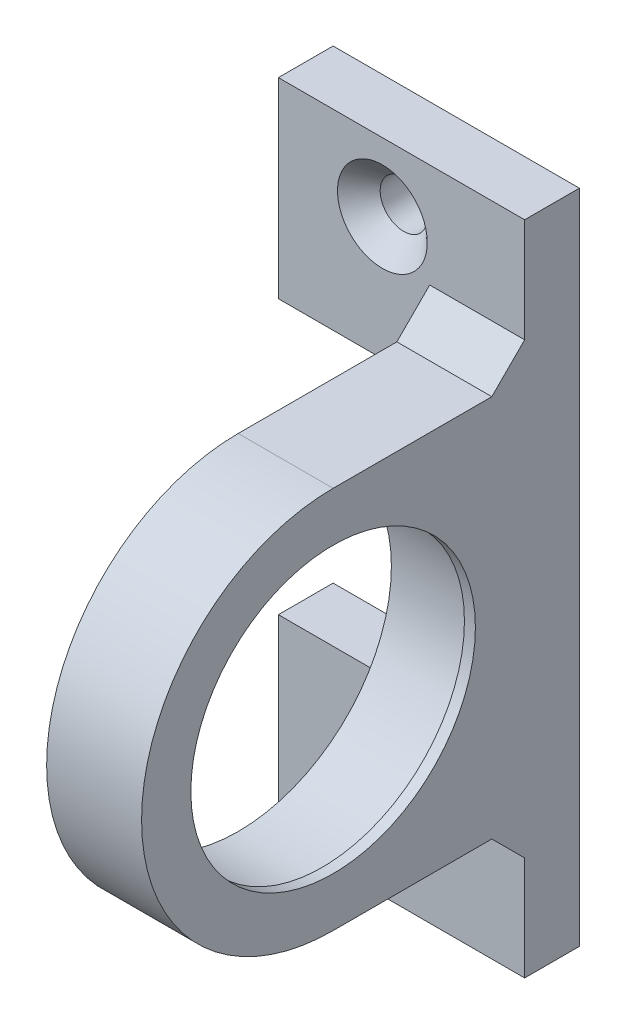
SolidWorks part; units mm, degrees
ref_plane "前视基准面" through (0, 0, 0) normal (0, 0, 1) x (1, 0, 0)
ref_plane "上视基准面" through (0, 0, 0) normal (0, 1, 0) x (1, 0, 0)
ref_plane "右视基准面" through (0, 0, 0) normal (1, 0, 0) x (0, 0, -1)
sketch "草图2" plane through (0, 0, 0) normal (0, 0, 1) x (1, 0, 0)
  line L0 (-14.7736, 24.3382) -> (-14.7736, -35.6618)
  line L1 (-14.7736, -35.6618) -> (30.2264, -35.6618)
  line L2 (7.7264, -35.6618) -> (7.7264, -18.1618)
  line L3 (21.55, -18.1618) -> (-6.0971, -18.1618)
  line L4 (-6.0971, -18.1618) -> (-6.0971, 6.8382)
  line L5 (-6.0971, 6.8382) -> (21.55, 6.8382)
  line L6 (7.7264, 6.8382) -> (7.7264, 24.3382)
  line L7 (30.2264, 24.3382) -> (-14.7736, 24.3382)
  line L8 (7.7264, 28.8603) -> (7.7264, -39.8897) construction
  line L9 (21.55, -18.1618) -> (21.55, 6.8382)
  line L10 (30.2264, 24.3382) -> (30.2264, -35.6618)
  line L11 (-18.1559, -5.6618) -> (33.2411, -5.6618) construction
  line L12 (44.0218, -5.6618) -> (44.0218, 26.2521) construction
  point P16 (-6.0971, -5.6618)
  point P17 (-14.7736, -5.6618)
  dimension "D1" = 45
  dimension "D2" = 25
  dimension "D3" = 60
extrude "凸台-拉伸2" add sketch "草图2" along normal blind 5 contours L6 L7 L0 L1 L2 L3 L4 L5 | L10 L7 L6 L5 L9 L3 L2 L1 region at (-3.5236, 23.6974, 0) region at (18.9764, 23.6974, 0)
sketch "草图4" plane through (0, 0, 5) normal (0, 0, 1) x (1, 0, 0)
  line L0 (-18.165, -5.6618) -> (33.9165, -5.6618) construction
  line L1 (-14.7736, 24.3382) -> (-14.7736, -35.6618) construction
  line L2 (-14.7736, -23.1618) -> (-6.0971, -23.1618)
  line L3 (-14.7736, -23.1618) -> (-14.7736, 11.8382)
  line L4 (-14.7736, 11.8382) -> (-6.0971, 11.8382)
  line L5 (-6.0971, -23.1618) -> (-6.0971, 11.8382)
  line L6 (-6.0971, -18.1618) -> (-6.0971, 6.8382) construction
  line L7 (7.7264, -39.813) -> (7.7264, 28.1228) construction
  line L8 (30.2264, 11.8382) -> (21.55, 11.8382)
  line L9 (21.55, -23.1618) -> (21.55, 11.8382)
  line L10 (30.2264, -23.1618) -> (21.55, -23.1618)
  line L11 (30.2264, -23.1618) -> (30.2264, 11.8382)
  point P17 (-14.7736, -5.6618)
  dimension "D1" = 35
extrude "凸台-拉伸15" add sketch "草图4" along normal blind 35
sketch "草图5" plane through (-14.7736, 0, 0) normal (-1, 0, 0) x (0, 0, 1)
  line L0 (0, -5.6618) -> (40, -5.6618)
  line L1 (0, 24.3382) -> (0, -35.6618) construction
  line L2 (40, 11.8382) -> (40, -23.1618) construction
  line L3 (22.5, 11.8382) -> (40, 11.8382)
  line L4 (40, 11.8382) -> (40, -23.1618)
  line L5 (40, -23.1618) -> (22.5, -23.1618)
  circle A0 centre (22.5, -5.6618) radius 17.5
  line M5 (5, -23.1618) -> (40, -23.1618)
  line M6 (40, -23.1618) -> (40, 11.8382)
  line M7 (40, 11.8382) -> (5, 11.8382)
  dimension "D1" = 35
extrude "切除-拉伸1" cut sketch "草图5" against normal blind 45 contours A0 M5 M6 | A0 M6 M7 region at (-14.7736, 7.9293, 36.0911) region at (-14.7736, -19.2528, 36.0911)
sketch "草图6" plane through (-14.7736, 0, 0) normal (-1, 0, 0) x (0, 0, 1)
  circle A0 centre (22.5, -5.6618) radius 14
  dimension "D1" = 28
extrude "切除-拉伸2" cut sketch "草图6" against normal blind 45
fillet "圆角1" radius 5 4 edges at (-6.0971, 6.8382, 2.5) (21.55, 6.8382, 2.5) (-6.0971, -18.1618, 2.5) (21.55, -18.1618, 2.5)
sketch "草图7" plane through (-6.0971, 0, 0) normal (1, 0, 0) x (0, 0, -1)
  circle A0 centre (-22.5, -5.6618) radius 15
  circle A1 centre (-22.5, -5.6618) radius 13
extrude "凸台-拉伸16" add sketch "草图7" against normal blind 1
sketch "草图8" plane through (21.55, 0, 0) normal (-1, 0, 0) x (0, 0, 1)
  circle A0 centre (22.5, -5.6618) radius 15
  circle A1 centre (22.5, -5.6618) radius 10
sketch "草图9" plane through (0, 0, 5) normal (0, 0, 1) x (1, 0, 0)
  line L0 (7.7264, 24.3382) -> (7.7264, -35.6618)
  line L13 (30.2264, 24.3382) -> (-14.7736, 24.3382) construction
  line L14 (-14.7736, -35.6618) -> (30.2264, -35.6618) construction
sketch "草图11" plane through (0, 0, 5) normal (0, 0, 1) x (1, 0, 0)
  line L0 (-14.7736, 18.0882) -> (30.2264, 18.0882)
  line L1 (-14.7736, 24.3382) -> (-14.7736, 11.8382) construction
  line L2 (30.2264, 24.3382) -> (30.2264, 11.8382) construction
  line L3 (7.7264, 24.3382) -> (7.7264, -35.6618) construction
  line L4 (30.2264, 24.3382) -> (-14.7736, 24.3382) construction
  line L5 (-14.7736, -35.6618) -> (30.2264, -35.6618) construction
  line L6 (7.7264, -5.6618) -> (45.6912, -5.6618) construction
  line L10 (-14.7736, -29.4118) -> (30.2264, -29.4118)
  line L11 (-14.7736, -23.1618) -> (-14.7736, -35.6618) construction
  point P4 (-1.7736, 18.0882)
  point P16 (-1.7736, -29.4118)
  point P18 (17.2264, -29.4118)
  point P25 (17.2264, 18.0882)
  dimension "D1" = 13
split "分割1" trim tools "草图9" bodies to split 111 resulting bodies 117 118
delete or keep bodies "实体-删除/保留 2" type delete bodies bodies 117
hole_wizard "打孔尺寸(%根据)内六角花形半沉头螺钉的类型1" positions "3D草图2" profile "草图13" countersink size "M6" standard "GB"
sketch3d "3D草图2"
  point P0 (17.2264, 18.0882, 5)
  point P3 (17.2264, -29.4118, 5)
sketch "草图13" plane through (17.2264, 18.0882, 5) normal (1, 0, 0) x (0, -1, 0)
  line L0 (0, 0) -> (0, 6.2919)
  line L1 (0, 6.2919) -> (2.15, 5)
  line L2 (2.15, 5) -> (2.15, 1.95)
  line L3 (2.15, 1.95) -> (4.1, 0)
  line L5 (4.1, 0) -> (0, 0)
  line L6 (-2.15, 1.95) -> (-4.1, 0) construction
  line L10 (0, 6.2919) -> (-2.15, 5) construction
  line L11 (0, -6.35) -> (0, 107.95) construction
  dimension "孔直径" = 4.3
  dimension "孔深度" = 5
  dimension "近端锥形沉头孔直径" = 8.2
  dimension "近端锥形沉头孔角度" = 90
  dimension "导头角度" = 118
ref_plane "基准面1" through (30.2264, 0, 0) normal (1, 0, 0) x (0, 0, -1)
sketch "草图14" plane through (30.2264, 0, 0) normal (1, 0, 0) x (0, 0, -1)
  circle A1 centre (-22.5, -5.6618) radius 14 construction
  circle A3 centre (-22.5, -5.6618) radius 14
extrude "拉伸-薄壁1" add sketch "草图14" against normal blind 1 thin thin type one direction reverse wall 1
chamfer "倒角1" distance 3 angle 45 2 edges at (25.8882, -23.1618, 5) (25.8882, 11.8382, 5)
